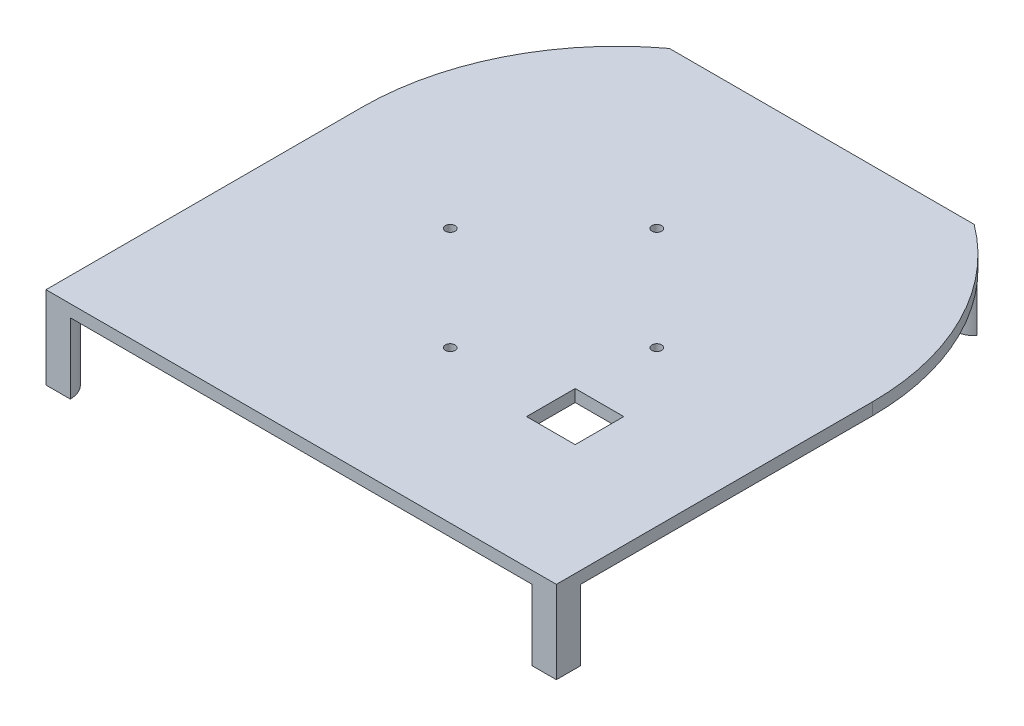
SolidWorks part; units mm, degrees
ref_plane "Front Plane" through (0, 0, 0) normal (0, 0, 1) x (1, 0, 0)
ref_plane "Top Plane" through (0, 0, 0) normal (0, 1, 0) x (1, 0, 0)
ref_plane "Right Plane" through (0, 0, 0) normal (1, 0, 0) x (0, 0, -1)
sketch "Sketch1" plane through (0, 0, 0) normal (0, 1, 0) x (1, 0, 0)
  line L1 (0, 0) -> (210, 0)
  line L2 (0, 0) -> (0, 130)
  line L3 (0, 130) -> (210, 130)
  line L4 (210, 0) -> (210, 130)
  circle A0 centre (105, 130) radius 105
  dimension "D1" = 130
  dimension "D2" = 210
extrude "Boss-Extrude1" add sketch "Sketch1" along normal blind 5 contours A0 L2 L1 L4 | L3 A0 | L3 A0 region at (2.4698, 0, -65) region at (105, 0, -174.5634) region at (105, 0, -85.4366)
sketch "Sketch2" plane through (0, 5, 0) normal (0, 1, 0) x (1, 0, 0)
  line L0 (0, 0) -> (210, 0) construction
  line L1 (0, 269.143) -> (213.8627, 269.143)
  line L2 (0, 269.143) -> (0, 214.23)
  line L3 (0, 214.23) -> (213.8627, 214.23)
  line L4 (213.8627, 269.143) -> (213.8627, 214.23)
  dimension "D1" = 214.23
extrude "Cut-Extrude1" cut sketch "Sketch2" against normal blind 5
sketch "Sketch3" plane through (0, 0, 0) normal (0, -1, 0) x (-1, 0, 0)
  circle A0 centre (-42.3078, 214.23) radius 8
  circle A1 centre (-167.6922, 214.23) radius 8
  circle A2 centre (-210, 0) radius 10
  circle A3 centre (0, 0) radius 10
  arc M1 (0, 130) -> (-42.3078, 214.23) centre (-105, 130) ccw
  line M2 (-42.3078, 214.23) -> (-167.6922, 214.23)
  arc M3 (-167.6922, 214.23) -> (-210, 130) centre (-105, 130) ccw
  line M4 (-210, 130) -> (-210, 0)
  line M5 (-210, 0) -> (0, 0)
  line M6 (0, 0) -> (0, 130)
  dimension "D1" = 20
  dimension "D2" = 20
  dimension "D3" = 16
  dimension "D4" = 16
extrude "Boss-Extrude2" add sketch "Sketch3" along normal blind 29 contours A2 M5 M4 | A1 M3 M2 | A0 M2 M1 | A3 M6 M5 region at (43.6426, 0, -210.3861) region at (166.3574, 0, -210.3861) region at (4.2441, 0, -4.2441) region at (205.7559, 0, -4.2441)
sketch "Sketch4" plane through (0, 0, 0) normal (0, -1, 0) x (1, 0, 0)
  line L0 (10, 0) -> (200, 0) construction
  line L1 (168, -84) -> (174, -84)
  line L2 (168, -84) -> (168, -90)
  line L3 (168, -90) -> (174, -90)
  line L4 (174, -84) -> (174, -90)
  line L5 (210, -10) -> (210, -130) construction
  dimension "D1" = 84
  dimension "D2" = 36
  dimension "D3" = 6
  dimension "D4" = 6
extrude "Boss-Extrude3" add sketch "Sketch4" along normal blind 30
sketch "Sketch5" plane through (0, 0, 0) normal (0, -1, 0) x (-1, 0, 0)
  line L0 (0, 10) -> (0, 130) construction
  line L1 (-75, 115) -> (-69, 115)
  line L2 (-75, 115) -> (-75, 109)
  line L3 (-75, 109) -> (-69, 109)
  line L4 (-69, 115) -> (-69, 109)
  line L5 (-10, 0) -> (-200, 0) construction
  dimension "D1" = 69
  dimension "D2" = 109
  dimension "D3" = 6
  dimension "D4" = 6
extrude "Boss-Extrude4" add sketch "Sketch5" along normal blind 30
fillet "Fillet1" radius 10 8 edges at (171, 0, -84) (168, 0, -87) (174, 0, -87) (171, 0, -90) (72, 0, -109) (69, 0, -112) (72, 0, -115) (75, 0, -112)
sketch "Sketch7" plane through (0, 5, 0) normal (0, 1, 0) x (1, 0, 0)
  line L0 (0, 0) -> (210, 0) construction
  circle A0 centre (103.829, 105) radius 50
  circle A1 centre (103.829, 147.5) radius 2
  circle A2 centre (146.329, 105) radius 2
  circle A3 centre (103.829, 62.5) radius 2
  circle A4 centre (61.329, 105) radius 2
  point P15 (103.829, 105)
  dimension "D2" = 100
  dimension "D3" = 42.5
  dimension "D1" = 105
  dimension "D4" = 4
extrude "Cut-Extrude2" cut sketch "Sketch7" against normal blind 29 contours A4 | A3 | A1 | A2 region at (103.829, 5, -147.5) region at (103.829, 5, -62.5) region at (61.329, 5, -105)
sketch "Sketch8" plane through (0, 5, 0) normal (0, 1, 0) x (1, 0, 0)
  line L1 (144.0918, 73.6512) -> (164.0918, 73.6512)
  line L2 (144.0918, 73.6512) -> (144.0918, 53.6512)
  line L3 (144.0918, 53.6512) -> (164.0918, 53.6512)
  line L4 (164.0918, 73.6512) -> (164.0918, 53.6512)
  dimension "D1" = 20
  dimension "D2" = 20
extrude "Cut-Extrude3" cut sketch "Sketch8" against normal blind 10
